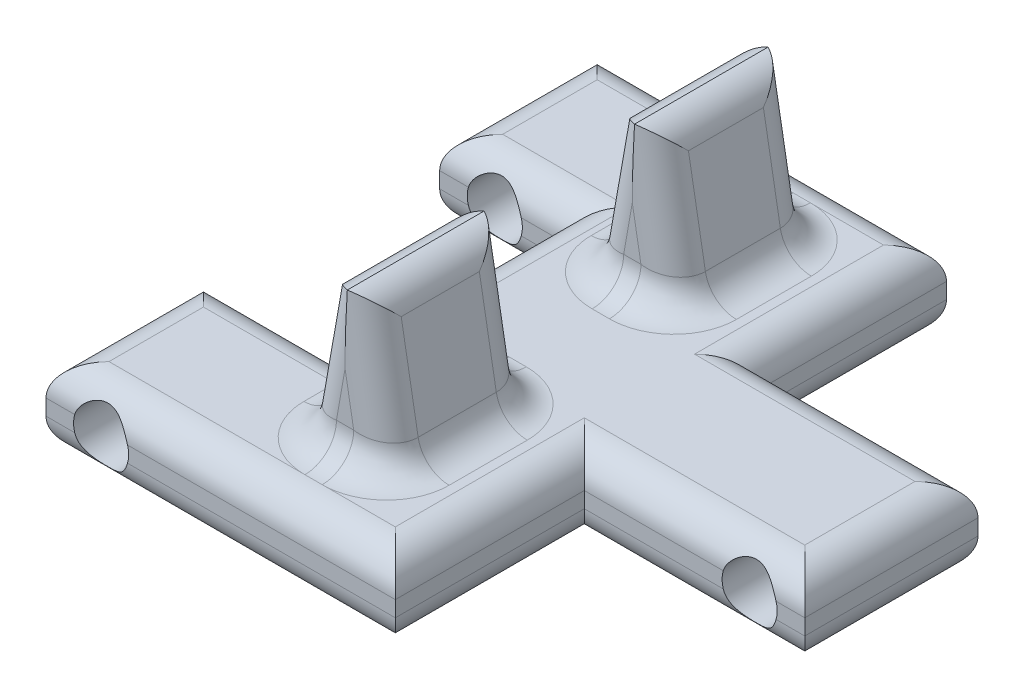
SolidWorks part; units mm, degrees
ref_plane "Front Plane" through (0, 0, 0) normal (0, 0, 1) x (1, 0, 0)
ref_plane "Top Plane" through (0, 0, 0) normal (0, 1, 0) x (1, 0, 0)
ref_plane "Right Plane" through (0, 0, 0) normal (1, 0, 0) x (0, 0, -1)
sketch "Sketch1" plane through (0, 0, 0) normal (0, 1, 0) x (1, 0, 0)
  line L0 (-14.9914, 7.3995) -> (-9.4914, 7.3995)
  line L1 (-14.9914, -17.6005) -> (7.1908, -17.6005)
  line L2 (-14.9914, -17.6005) -> (-14.9914, -7.6005)
  line L3 (-14.9914, 17.3995) -> (7.1908, 17.3995)
  line L7 (-6.9914, 7.3995) -> (-6.9914, 2.5018)
  line L8 (-6.9914, -7.6005) -> (-9.4914, -7.6005)
  line L9 (-14.9914, 7.3995) -> (-14.9914, 17.3995)
  line L10 (7.1908, 17.3995) -> (7.1908, 5.3995)
  line L12 (7.1908, -17.6005) -> (7.1908, -5.6005)
  line L28 (-6.9914, -2.5018) -> (-6.9914, -7.6005)
  line L31 (-9.4914, 7.3995) -> (-6.9914, 7.3995)
  line L32 (-9.4914, -7.6005) -> (-14.9914, -7.6005)
  line L33 (-6.9914, 2.5018) -> (-6.9914, -2.5018)
  line L34 (7.1908, 5.3995) -> (21.1908, 5.3995)
  line L35 (21.1908, 5.3995) -> (21.1908, -5.6005)
  line L36 (21.1908, -5.6005) -> (7.1908, -5.6005)
  point P0 (0, 0)
  dimension "D1" = 14
  dimension "D2" = 35
  dimension "D3" = 10
  dimension "D4" = 12
  dimension "D5" = 8
  dimension "D9" = 2.5
extrude "Boss-Extrude1" add sketch "Sketch1" along normal blind 5
sketch "Sketch5" plane through (0, 0, 17.6005) normal (0, 0, 1) x (1, 0, 0)
  line L0 (-17.6008, 2.5) -> (1.9314, 2.5) construction
  line L1 (-6.9914, 0) -> (-14.9914, 0) construction
  line L2 (-6.9914, 5) -> (-14.9914, 5) construction
  line L4 (-14.9914, 5) -> (-14.9914, 0) construction
  circle A0 centre (-11.4914, 2.5) radius 1.75
  dimension "D1" = 3.5
  dimension "2" = 3.5
extrude "Cut-Extrude1" cut sketch "Sketch5" against normal blind 42
sketch "Sketch6" plane through (0, 0, 5.6005) normal (0, 0, 1) x (1, 0, 0)
  line L0 (26.3292, 2.5) -> (6.5316, 2.5) construction
  line L1 (7.1908, 5) -> (21.1908, 5) construction
  line L2 (7.1908, 0) -> (21.1908, 0) construction
  line L3 (21.1908, 5) -> (21.1908, 0) construction
  circle A0 centre (17.6908, 2.5) radius 1.75
  dimension "D1" = 3.5
  dimension "D2" = 3.5
extrude "Cut-Extrude2" cut sketch "Sketch6" against normal blind 19
sketch "Sketch9" plane through (0, 0, 17.6005) normal (0, 0, 1) x (1, 0, 0)
  line L0 (0, 8.3909) -> (0, -6.7923) construction
  line L1 (-2.9321, 5) -> (-1.274, 14.4032)
  line L2 (-14.9914, 5) -> (7.1908, 5) construction
  line L3 (-1.274, 14.4032) -> (1.274, 14.4032)
  line L4 (1.274, 14.4032) -> (2.9321, 5)
  line L5 (2.9321, 5) -> (-2.9321, 5)
  dimension "D1" = 100
extrude "Boss-Extrude3" add sketch "Sketch9" against normal blind 27 from offset 4 offset against normal yes
sketch "Sketch10" plane through (21.1908, 0, 0) normal (1, 0, 0) x (0, 0, -1)
  line L0 (-5.6005, 5) -> (5.3995, 5) construction
  line L1 (-4.6394, 17.2402) -> (4.6394, 17.2402)
  line L2 (-4.6394, 17.2402) -> (-4.6394, 5)
  line L3 (-4.6394, 5) -> (4.6394, 5)
  line L4 (4.6394, 17.2402) -> (4.6394, 5)
  line L5 (0, 15.8304) -> (0, -3.5317) construction
extrude "Cut-Extrude4" cut sketch "Sketch10" against normal blind 27
fillet "Fillet3" radius 2 44 edges at (-1.274, 14.4032, 9.1199) (-2.1031, 9.7016, 13.6005) (-2.1031, 9.7016, 4.6394) (-2.1031, 9.7016, -13.3995) (-1.274, 14.4032, -9.0194) (-2.1031, 9.7016, -4.6394) (1.274, 14.4032, -9.0194) (2.1031, 9.7016, -13.3995) (2.1031, 9.7016, -4.6394) (2.1031, 9.7016, 13.6005) (1.274, 14.4032, 9.1199) (2.1031, 9.7016, 4.6394) (21.1908, 0, 0.1005) (14.1908, 0, -5.3995) (7.1908, 0, -11.3995) (-3.9003, 0, -17.3995) (-14.9914, 0, -12.3995) (-10.9914, 0, -7.3995) (-6.9914, 0, 0.1005) (-10.9914, 0, 7.6005) (-14.9914, 0, 12.6005) (-3.9003, 0, 17.6005) (7.1908, 0, 11.6005) (14.1908, 0, 5.6005) (14.1908, 5, 5.6005) (7.1908, 5, 11.6005) (-3.9003, 5, 17.6005) (-14.9914, 5, 12.6005) (-10.9914, 5, 7.6005) (-6.9914, 5, 0.1005) (-10.9914, 5, -7.3995) (-14.9914, 5, -12.3995) (-3.9003, 5, -17.3995) (7.1908, 5, -11.3995) (14.1908, 5, -5.3995) (21.1908, 5, 0.1005) (2.9321, 5, -9.0194) (0, 5, -13.3995) (-2.9321, 5, -9.0194) (0, 5, -4.6394) (-2.9321, 5, 9.1199) (0, 5, 13.6005) (2.9321, 5, 9.1199) (0, 5, 4.6394)
